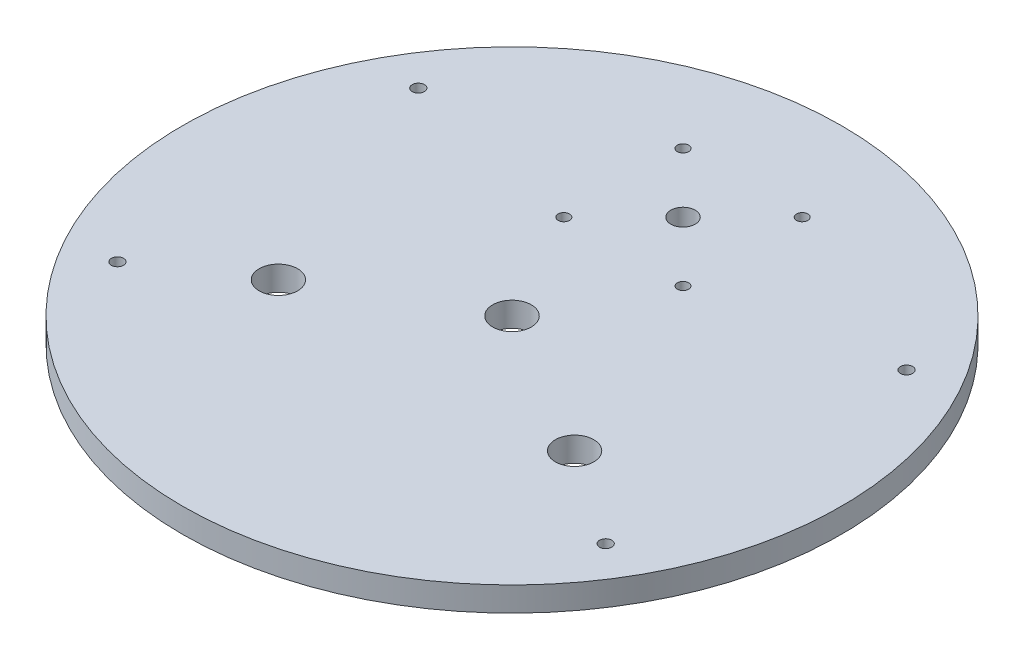
SolidWorks part; units mm, degrees
ref_plane "Front Plane" through (0, 0, 0) normal (0, 0, 1) x (1, 0, 0)
ref_plane "Top Plane" through (0, 0, 0) normal (0, 1, 0) x (1, 0, 0)
ref_plane "Right Plane" through (0, 0, 0) normal (1, 0, 0) x (0, 0, -1)
sketch "Sketch1" plane through (0, 0, 0) normal (0, 1, 0) x (1, 0, 0)
  circle A0 centre (0, 0) radius 85.725
  dimension "D1" = 171.45
extrude "Boss-Extrude1" add sketch "Sketch1" along normal blind 6.35
sketch "Sketch2" plane through (0, 6.35, 0) normal (0, 1, 0) x (1, 0, 0)
  line L0 (-63.5, 39.1325) -> (-63.5, -39.1325) construction
  line L1 (-63.5, -39.1325) -> (63.5, -39.1325) construction
  line L2 (63.5, -39.1325) -> (63.5, 39.1325) construction
  line L3 (63.5, 39.1325) -> (-63.5, 39.1325) construction
  circle A0 centre (-63.5, 39.1325) radius 1.5875
  circle A1 centre (63.5, 39.1325) radius 1.5875
  circle A2 centre (-63.5, -39.1325) radius 1.5875
  circle A3 centre (63.5, -39.1325) radius 1.5875
  dimension "D1" = 3.175
  dimension "D2" = 3.175
  dimension "D3" = 127
  dimension "D4" = 3.175
  dimension "D5" = 3.175
  dimension "D6" = 78.265
  dimension "D8" = 39.1325
  dimension "D9" = 63.5
extrude "Cut-Extrude1" cut sketch "Sketch2" against normal up to next
sketch "Sketch3" plane through (0, 6.35, 0) normal (0, 1, 0) x (1, 0, 0)
  line L0 (0, 44.4823) -> (0, 0) construction
  line L1 (0, 0) -> (-38.5228, -22.2411) construction
  line L2 (0, 0) -> (38.5228, -22.2411) construction
  circle A0 centre (0, 44.4823) radius 3.175
  circle A1 centre (-38.5228, -22.2411) radius 5
  circle A2 centre (38.5228, -22.2411) radius 5
  dimension "D1" = 6.35
  dimension "D5" = 10
  dimension "D6" = 10
  dimension "D2" = 44.4823
  dimension "D3" = 120
  dimension "D4" = 120
extrude "Cut-Extrude2" cut sketch "Sketch3" against normal up to next contours A2 | A0 | A1 region at (38.5228, 6.35, 22.2411)
ref_axis "Axis1" through (0, 6.35, 0) along (0, -1, 0)
sketch "Sketch5" plane through (0, 6.35, 0) normal (0, 1, 0) x (1, 0, 0)
  line L1 (-15.5003, 59.9826) -> (15.5003, 59.9826) construction
  line L2 (-15.5003, 59.9826) -> (-15.5003, 28.9819) construction
  line L3 (-15.5003, 28.9819) -> (15.5004, 28.9819) construction
  line L4 (15.5003, 59.9826) -> (15.5004, 28.9819) construction
  line L5 (-15.5003, 59.9826) -> (15.5004, 28.9819) construction
  line L6 (-15.5003, 28.9819) -> (15.5003, 59.9826) construction
  circle A0 centre (0, 44.4823) radius 3.175 construction
  circle A1 centre (0, 44.4823) radius 3.175 construction
  circle A2 centre (-15.5003, 59.9826) radius 1.4732
  circle A3 centre (15.5003, 59.9826) radius 1.4732
  circle A4 centre (-15.5003, 28.9819) radius 1.4732
  circle A5 centre (15.5004, 28.9819) radius 1.4732
  dimension "D3" = 2.9464
  dimension "D4" = 2.9464
  dimension "D5" = 2.9464
  dimension "D6" = 2.9464
  dimension "D1" = 31.0007
  dimension "D2" = 31.0007
extrude "Cut-Extrude3" cut sketch "Sketch5" against normal up to next
sketch "Sketch6" plane through (0, 6.35, 0) normal (0, 1, 0) x (1, 0, 0)
  circle A0 centre (0, 0) radius 5.0165
  dimension "D1" = 10.033
extrude "center_hole" cut sketch "Sketch6" against normal up to next
equation "\"spur_gear_shaft_dist\"=1.75127"
equation "\"D2@Sketch3\"=\"spur_gear_shaft_dist\""
